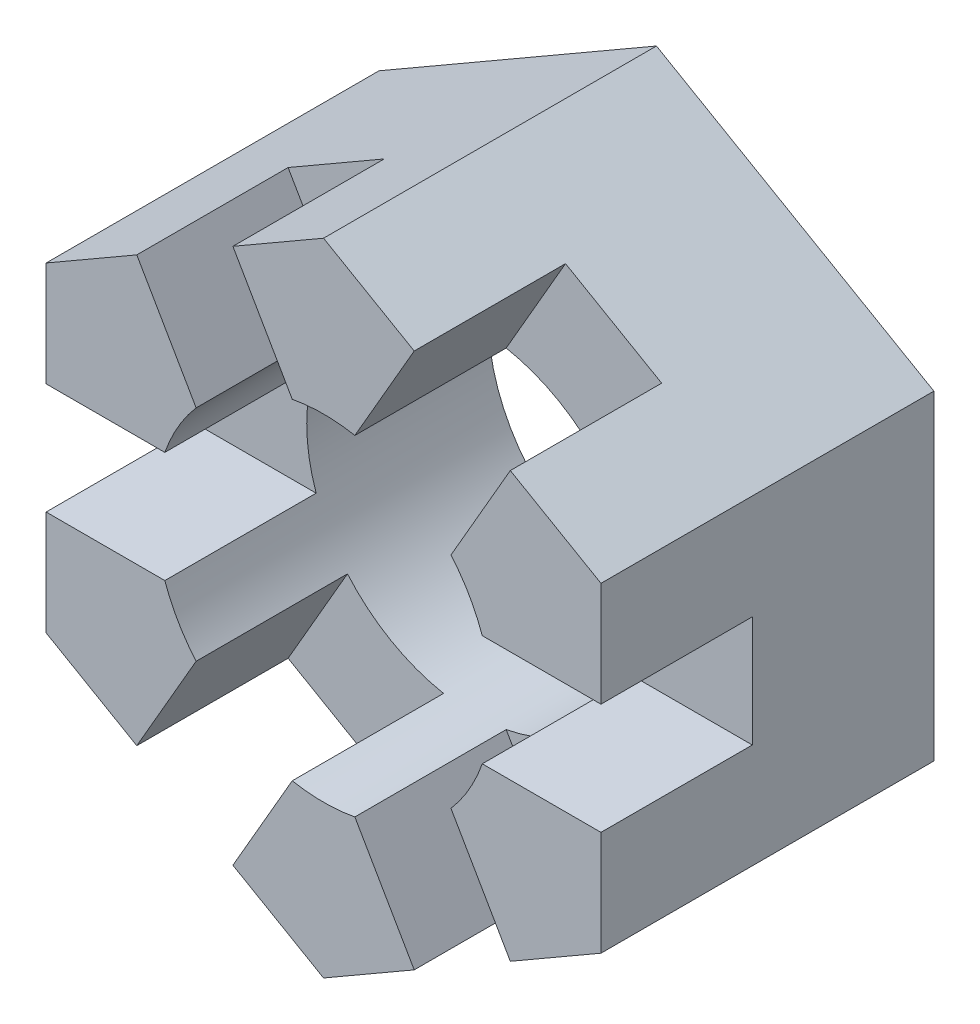
SolidWorks part; units mm, degrees
ref_plane "前视基准面" through (0, 0, 0) normal (0, 0, 1) x (1, 0, 0)
ref_plane "上视基准面" through (0, 0, 0) normal (0, 1, 0) x (1, 0, 0)
ref_plane "右视基准面" through (0, 0, 0) normal (1, 0, 0) x (0, 0, -1)
sketch "草图1" plane through (0, 0, 0) normal (0, 0, 1) x (1, 0, 0)
  line L0 (0, 6.3292) -> (0, 5.3413) construction
  line L1 (0, -9.5263) -> (8.25, -4.7631)
  line L2 (8.25, -4.7631) -> (8.25, 4.7631)
  line L3 (8.25, 4.7631) -> (0, 9.5263)
  line L4 (0, 9.5263) -> (-8.25, 4.7631)
  line L5 (-8.25, 4.7631) -> (-8.25, -4.7631)
  line L6 (-8.25, -4.7631) -> (0, -9.5263)
  line L7 (-6.9527, 0) -> (-6.1169, 0) construction
  line L8 (-8.25, 1.65) -> (-4.7199, 1.65)
  line L9 (-8.25, -1.65) -> (-4.7199, -1.65)
  line L10 (-2.6961, 7.9697) -> (-0.931, 4.9126)
  line L11 (-5.5539, 6.3197) -> (-3.7889, 3.2626)
  line L12 (5.5539, 6.3197) -> (3.7889, 3.2626)
  line L13 (2.6961, 7.9697) -> (0.931, 4.9126)
  line L14 (8.25, -1.65) -> (4.7199, -1.65)
  line L15 (8.25, 1.65) -> (4.7199, 1.65)
  line L16 (2.6961, -7.9697) -> (0.931, -4.9126)
  line L17 (5.5539, -6.3197) -> (3.7889, -3.2626)
  line L18 (-5.5539, -6.3197) -> (-3.7889, -3.2626)
  line L19 (-2.6961, -7.9697) -> (-0.931, -4.9126)
  circle A0 centre (0, 0) radius 8.25 construction
  circle A1 centre (0, 0) radius 5
  dimension "D2" = 3.3
  dimension "D3" = 10
  dimension "D1" = 16.5
  dimension "D4" = 6
extrude "凸台-拉伸1" add sketch "草图1" along normal blind 4.5 contours A1 L9 L5 L6 L18 | A1 L19 L6 L1 L16 | A1 L17 L1 L2 L14 | A1 L15 L2 L3 L12 | A1 L13 L3 L4 L10 | A1 L11 L4 L5 L8 region at (0, -7.1992, 0) region at (6.2347, -3.5996, 0) region at (-6.2347, -3.5996, 0) region at (6.2347, 3.5996, 0) region at (-6.2347, 3.5996, 0) region at (0, 7.1992, 0)
extrude "凸台-拉伸2" add sketch "草图1<4>" against normal blind 5.4 contours A1 L11 L4 L5 L8 | A1 L10 L4 L11 | A1 L13 L3 L4 L10 | A1 L12 L3 L13 | A1 L15 L2 L3 L12 | A1 L14 L2 L15 | A1 L17 L1 L2 L14 | A1 L16 L1 L17 | A1 L19 L6 L1 L16 | A1 L18 L6 L19 | A1 L9 L5 L6 L18 | A1 L8 L5 L9 region at (0, -7.1992, 0) region at (3.2889, -5.6966, 0) region at (-3.2889, -5.6966, 0) region at (6.2347, -3.5996, 0) region at (-6.2347, -3.5996, 0) region at (6.5778, 0, 0) region at (-6.5778, 0, 0) region at (6.2347, 3.5996, 0) region at (-6.2347, 3.5996, 0) region at (-3.2889, 5.6966, 0) region at (3.2889, 5.6966, 0) region at (0, 7.1992, 0)
sketch "草图1<4>" plane through (0, 0, 0) normal (0, 0, 1) x (1, 0, 0) same geometry as "草图1"
